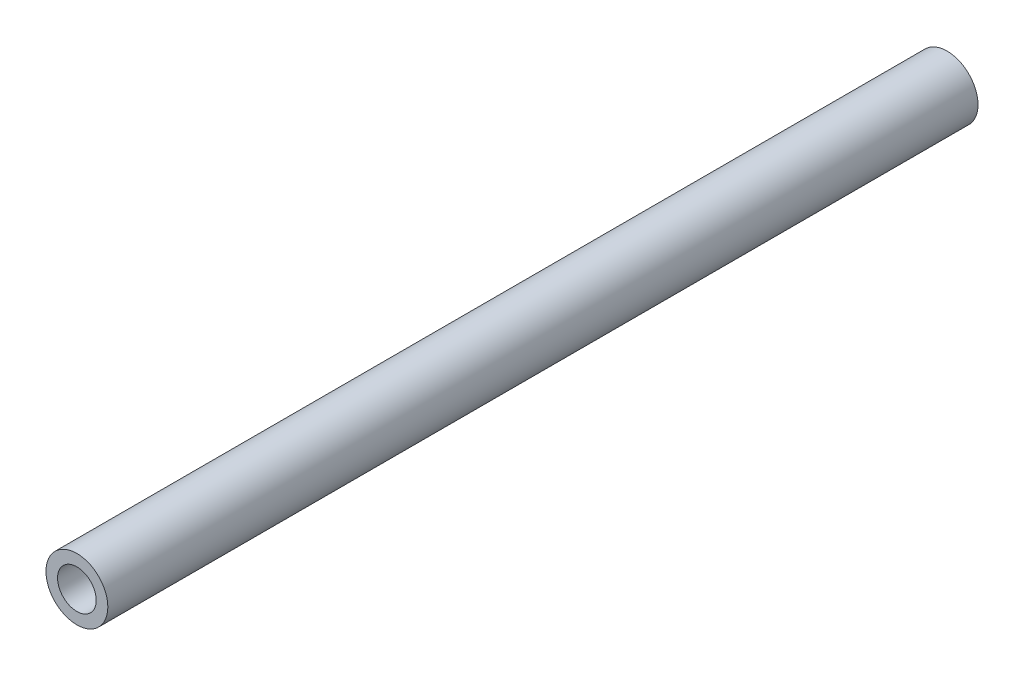
SolidWorks part; units mm, degrees
material "1.0545 (S355N)"
ref_plane "Płaszczyzna przednia" through (0, 0, 0) normal (0, 0, 1) x (1, 0, 0)
ref_plane "Płaszczyzna górna" through (0, 0, 0) normal (0, 1, 0) x (1, 0, 0)
ref_plane "Płaszczyzna prawa" through (0, 0, 0) normal (1, 0, 0) x (0, 0, -1)
sketch "Szkic1" plane through (0, 0, 0) normal (0, 0, 1) x (1, 0, 0)
  circle A0 centre (0, 0) radius 8
  circle A1 centre (0, 0) radius 4
  dimension "D1" = 16
  dimension "D2" = 4
extrude "Dodanie-wyciągnięcie1" add sketch "Szkic1" along normal mid plane 225
sketch "Szkic2" plane through (0, 0, 112.5) normal (0, 0, 1) x (1, 0, 0)
  circle A0 centre (0, 0) radius 5
  circle A2 centre (0, 0) radius 4 construction
  dimension "D1" = 1
extrude "Wytnij-wyciągnięcie1" cut sketch "Szkic2" against normal blind 40
sketch "Szkic3" plane through (0, 0, -112.5) normal (0, 0, -1) x (-1, 0, 0)
  circle A0 centre (0, 0) radius 5
  circle A1 centre (0, 0) radius 4 construction
  dimension "D1" = 1
extrude "Wytnij-wyciągnięcie2" cut sketch "Szkic3" against normal blind 30
